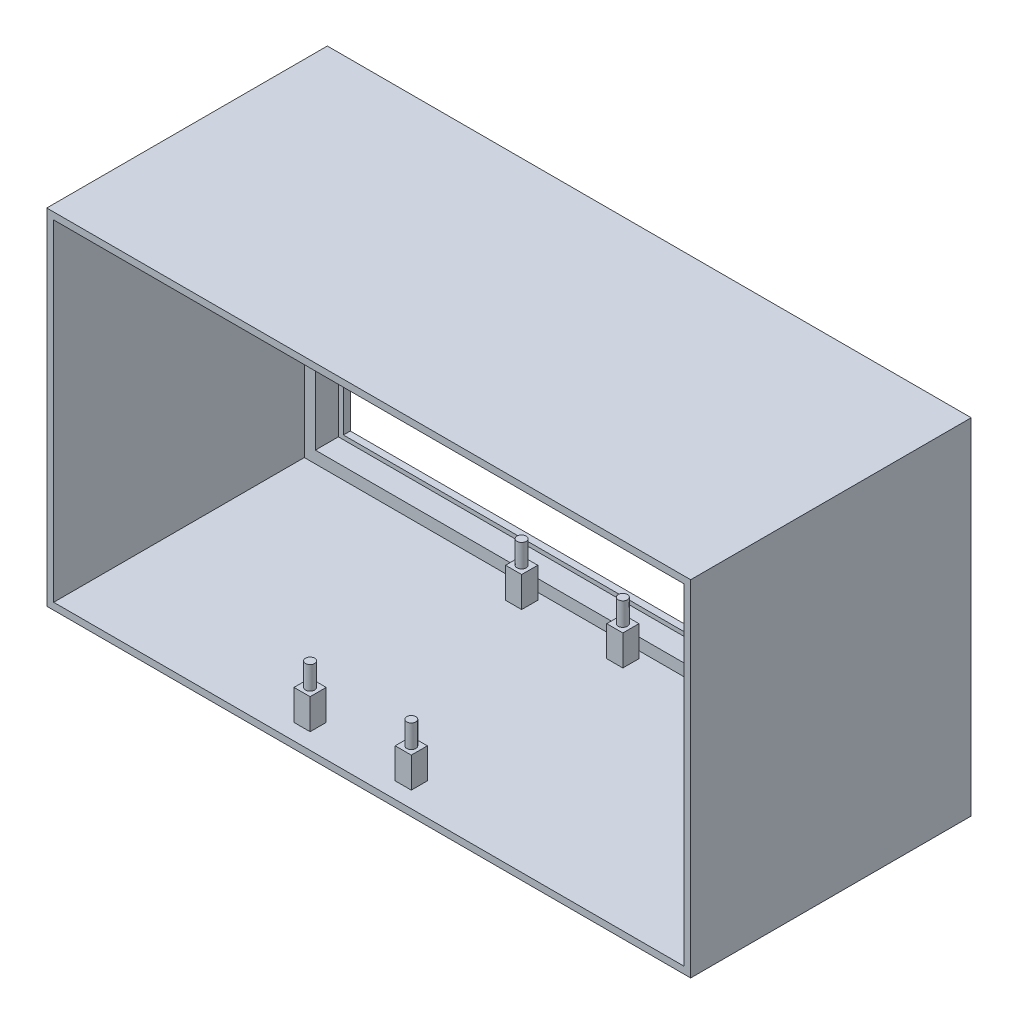
SolidWorks part; units mm, degrees
ref_plane "前视基准面" through (0, 0, 0) normal (0, 0, 1) x (1, 0, 0)
ref_plane "上视基准面" through (0, 0, 0) normal (0, 1, 0) x (1, 0, 0)
ref_plane "右视基准面" through (0, 0, 0) normal (1, 0, 0) x (0, 0, -1)
other "Configuration Table"
sketch "草图1" plane through (0, 0, 0) normal (0, 0, 1) x (1, 0, 0)
  line L1 (-50.7518, 32.0879) -> (89.2482, 32.0879)
  line L2 (-50.7518, 32.0879) -> (-50.7518, -42.9121)
  line L3 (-50.7518, -42.9121) -> (89.2482, -42.9121)
  line L4 (89.2482, 32.0879) -> (89.2482, -42.9121)
  dimension "D1" = 75
  dimension "D2" = 140
extrude "凸台-拉伸1" add sketch "草图1" along normal blind 61
shell "抽壳1" thickness 1.5 removed face at (19.2482, -5.4121, 61)
sketch "草图3" plane through (0, 0, 0) normal (0, 0, -1) x (-1, 0, 0)
  line L0 (-89.2482, -42.9121) -> (-89.2482, 32.0879) construction
  line L1 (-84.2482, 27.0879) -> (45.7518, 27.0879)
  line L2 (-84.2482, 27.0879) -> (-84.2482, -37.9121)
  line L3 (-84.2482, -37.9121) -> (45.7518, -37.9121)
  line L4 (45.7518, 27.0879) -> (45.7518, -37.9121)
  line L5 (50.7518, -42.9121) -> (-89.2482, -42.9121) construction
  dimension "D1" = 65
  dimension "D2" = 130
  dimension "D3" = 5
  dimension "D4" = 5
extrude "切除-拉伸1" cut sketch "草图3" against normal through all
sketch "草图4" plane through (0, 0, 1.5) normal (0, 0, 1) x (1, 0, 0)
  line L0 (87.7482, -41.4121) -> (87.7482, 30.5879) construction
  line L1 (-49.2518, -41.4121) -> (87.7482, -41.4121)
  line L2 (-49.2518, -41.4121) -> (-49.2518, -38.8121)
  line L3 (-49.2518, -38.8121) -> (87.7482, -38.8121)
  line L4 (87.7482, -41.4121) -> (87.7482, -38.8121)
  line L6 (-49.2518, 27.2879) -> (87.7482, 27.2879)
  line L7 (-49.2518, 27.2879) -> (-49.2518, 30.5879)
  line L8 (-49.2518, 30.5879) -> (87.7482, 30.5879)
  line L9 (87.7482, 27.2879) -> (87.7482, 30.5879)
  dimension "D1" = 2.6
  dimension "D2" = 3.3
extrude "凸台-拉伸2" add sketch "草图4" along normal blind 5
sketch "草图5" plane through (0, 0, 1.5) normal (0, 0, 1) x (1, 0, 0)
  line L0 (87.7482, -38.8121) -> (-49.2518, -38.8121) construction
  line L1 (-49.2518, 30.5879) -> (-46.8518, 30.5879)
  line L2 (-49.2518, 30.5879) -> (-49.2518, -38.8121)
  line L3 (-49.2518, -38.8121) -> (-46.8518, -38.8121)
  line L4 (-46.8518, 30.5879) -> (-46.8518, -38.8121)
  line L6 (87.7482, 30.5879) -> (85.3482, 30.5879)
  line L7 (87.7482, 30.5879) -> (87.7482, -38.8121)
  line L8 (87.7482, -38.8121) -> (85.3482, -38.8121)
  line L9 (85.3482, 30.5879) -> (85.3482, -38.8121)
  dimension "D1" = 2.4
  dimension "D2" = 2.4
extrude "凸台-拉伸3" add sketch "草图5" along normal blind 5
sketch "草图6" plane through (0, -41.4121, 0) normal (0, 1, 0) x (1, 0, 0)
  line L0 (19.2482, -6.5) -> (19.2482, -46.8623) construction
  line L1 (-49.2518, -6.5) -> (87.7482, -6.5) construction
  line L3 (58.2482, -51.5) -> (-19.7518, -51.5)
  line L4 (58.2482, -51.5) -> (58.2482, -9.5)
  line L5 (58.2482, -9.5) -> (-19.7518, -9.5)
  line L6 (-19.7518, -51.5) -> (-19.7518, -9.5)
  line L7 (58.2482, -51.5) -> (-19.7518, -9.5) construction
  line L8 (58.2482, -9.5) -> (-19.7518, -51.5) construction
  point P4 (19.2482, -30.5)
  dimension "D1" = 42
  dimension "D2" = 78
  dimension "D3" = 24
extrude "切除-拉伸2" [suppressed] cut sketch "草图6" against normal through all
sketch "草图20" plane through (0, -41.4121, 0) normal (0, 1, 0) x (1, 0, 0)
  line L0 (-0.5, -11.5) -> (-0.5, -8)
  line L1 (-0.5, -57.5) -> (3, -57.5)
  line L2 (-0.5, -57.5) -> (-0.5, -54)
  line L3 (-0.5, -8) -> (3, -8)
  line L4 (25, -57.5) -> (25, -54)
  line L5 (3, -55.75) -> (21.5, -55.75) construction
  line L6 (-0.5, -57.5) -> (3, -57.5)
  line L7 (-0.5, -57.5) -> (-0.5, -54)
  line L8 (-0.5, -54) -> (3, -54)
  line L9 (3, -57.5) -> (3, -54)
  line L10 (25, -57.5) -> (21.5, -57.5)
  line L11 (25, -57.5) -> (25, -54)
  line L12 (25, -54) -> (21.5, -54)
  line L13 (21.5, -57.5) -> (21.5, -54)
  line L14 (25, -8) -> (21.5, -8)
  line L15 (25, -8) -> (25, -11.5)
  line L16 (25, -11.5) -> (21.5, -11.5)
  line L17 (21.5, -8) -> (21.5, -11.5)
  line L18 (-0.5, -8) -> (3, -8)
  line L19 (-0.5, -8) -> (-0.5, -11.5)
  line L20 (-0.5, -11.5) -> (3, -11.5)
  line L21 (3, -8) -> (3, -11.5)
  line L22 (21.5, -8) -> (25, -8)
  line L23 (25, -11.5) -> (25, -8)
  line L24 (21.5, -57.5) -> (25, -57.5)
  point P18 (12.25, -55.75)
  dimension "D2" = 25.5
  dimension "D3" = 3.5
  dimension "D4" = 3.5
  dimension "D5" = 3.5
  dimension "D6" = 3.5
  dimension "D7" = 3.5
  dimension "D8" = 3.5
  dimension "D9" = 3.5
  dimension "D10" = 3.5
  dimension "D11" = 42.5
extrude "凸台-拉伸4" add sketch "草图20" along normal blind 6.6 contours L1 L9 L8 L2 | L21 L3 L0 L20 | L14 L17 L16 L15 | L11 L10 L13 L12 region at (1.25, -41.4121, 9.75) region at (1.25, -41.4121, 55.75) region at (23.25, -41.4121, 9.75)
sketch "草图21" plane through (0, -34.8121, 0) normal (0, 1, 0) x (1, 0, 0)
  circle A2 centre (1.25, -55.75) radius 1
  circle A3 centre (1.25, -9.75) radius 1
  circle A4 centre (23.25, -9.75) radius 1
  circle A5 centre (23.25, -55.75) radius 1
  dimension "D1" = 2
  dimension "D2" = 2
  dimension "D3" = 2
  dimension "D4" = 2
extrude "凸台-拉伸5" add sketch "草图21" along normal blind 5
